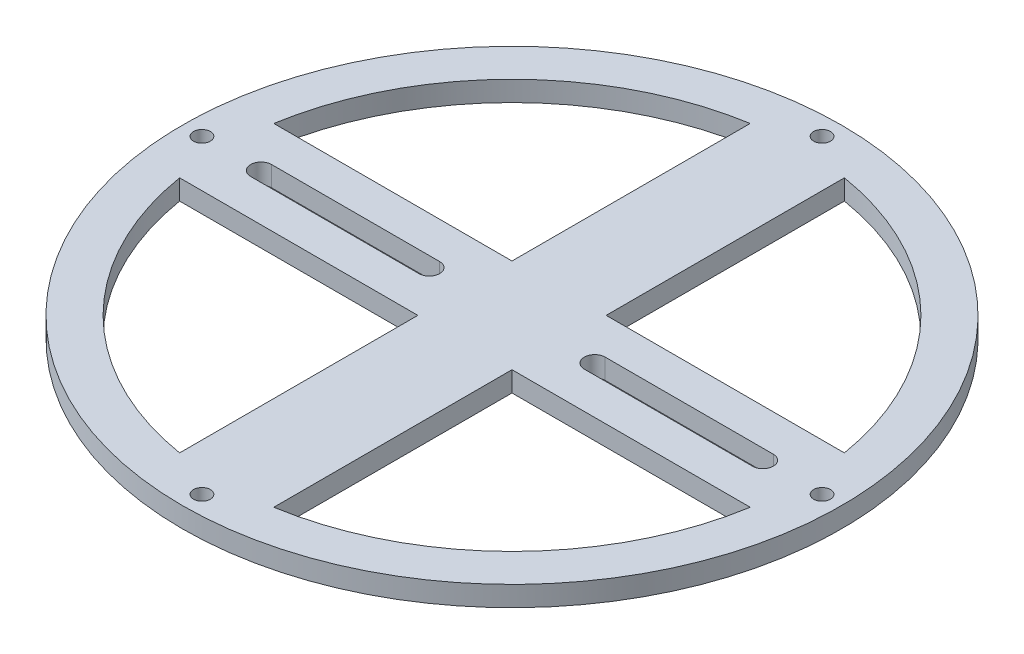
SolidWorks part; units mm, degrees
ref_plane "前视" through (0, 0, 0) normal (0, 0, 1) x (1, 0, 0)
ref_plane "上视" through (0, 0, 0) normal (0, 1, 0) x (1, 0, 0)
ref_plane "右视" through (0, 0, 0) normal (1, 0, 0) x (0, 0, -1)
sketch "草图1" plane through (0, 0, 0) normal (0, 1, 0) x (1, 0, 0)
  line L0 (-66.1799, 0) -> (81.937, 0) construction
  circle A0 centre (0, 0) radius 49
  dimension "D1" = 98
extrude "凸台-拉伸1" add sketch "草图1" along normal blind 3
sketch "草图2" plane through (0, 3, 0) normal (0, 1, 0) x (1, 0, 0)
  line L0 (0, 51.8724) -> (0, -53.4296) construction
  line L1 (-65.7201, 0) -> (62.0667, 0) construction
  circle A1 centre (0, 46.1) radius 1.25
  dimension "D1" = 46.1
  dimension "D2" = 2.5
sketch "草图5" plane through (0, 3, 0) normal (0, 1, 0) x (1, 0, 0)
  line L0 (-59.7985, 0) -> (61.0663, 0) construction
  line L1 (7, -53.9211) -> (7, 55.1109) construction
  line L2 (-63.602, 7) -> (62.9681, 7) construction
  line L4 (7, 42.42) -> (7, 7)
  line L5 (7, 7) -> (42.42, 7)
  arc A0 (7, 42.42) -> (42.42, 7) centre (0, 0) cw
  dimension "D1" = 7
  dimension "D2" = 7
extrude "切除-拉伸3" cut sketch "草图5" against normal through all
sketch "草图6" plane through (0, 3, 0) normal (0, 1, 0) x (1, 0, 0)
  line L0 (-12.3, 0) -> (-37.3, 0) construction
  line L1 (-65.7201, 0) -> (62.0667, 0) construction
  line L2 (-12.3, -1.55) -> (-37.3, -1.55)
  line L3 (-12.3, 1.55) -> (-37.3, 1.55)
  arc A0 (-12.3, -1.55) -> (-12.3, 1.55) centre (-12.3, 0) ccw
  arc A1 (-37.3, 1.55) -> (-37.3, -1.55) centre (-37.3, 0) ccw
  point P4 (-24.8, 0)
  dimension "D1" = 12.3
  dimension "D2" = 25
extrude "切除-拉伸4" cut sketch "草图6" against normal through all
pattern_circular "阵列(圆周)4" count 2 over 360 about axis through (0, 3, 0) along (0, -1, 0) of "切除-拉伸4"
extrude "切除-拉伸5" cut sketch "草图2" against normal through all
pattern_circular "阵列(圆周)5" count 4 over 360 about axis through (0, 3, 0) along (0, -1, 0) of "切除-拉伸5"
sketch "草图7" plane through (0, 3, 0) normal (0, 1, 0) x (1, 0, 0)
  line L0 (24.8, 2.9726) -> (24.8, -3.72) construction
pattern_circular "阵列(圆周)6" count 4 over 360 about axis through (0, 3, 0) along (0, -1, 0) of "切除-拉伸3"
